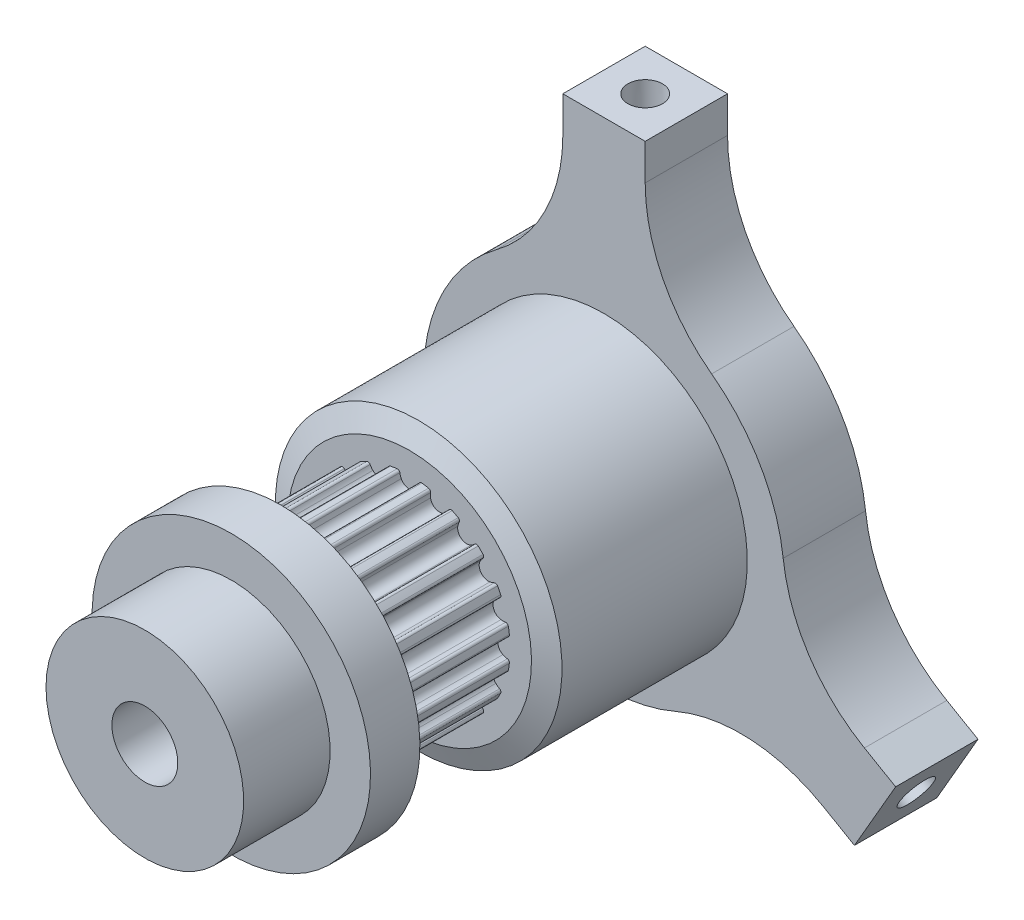
SolidWorks part; units mm, degrees
ref_plane "Front Plane" through (0, 0, 0) normal (0, 0, 1) x (1, 0, 0)
ref_plane "Top Plane" through (0, 0, 0) normal (0, 1, 0) x (1, 0, 0)
ref_plane "Right Plane" through (0, 0, 0) normal (1, 0, 0) x (0, 0, -1)
sketch "Sketch10" plane through (0, 0, 0) normal (0, 0, 1) x (1, 0, 0)
  circle A0 centre (0, 0) radius 2 construction
  dimension "D1" = 4
sketch "Sketch1" plane through (0, 0, 0) normal (0, 0, 1) x (1, 0, 0)
  line L5 (7.9825, -7.4955) -> (15.2045, -11.6651)
  line L6 (10.4825, -3.1653) -> (17.7045, -7.3349)
  line L7 (15.2045, -11.6651) -> (17.7045, -7.3349)
  line L9 (-10.4825, -3.1653) -> (-17.7045, -7.3349)
  line L10 (-7.9825, -7.4955) -> (-15.2045, -11.6651)
  line L11 (-17.7045, -7.3349) -> (-15.2045, -11.6651)
  line L13 (-2.5, 10.6608) -> (-2.5, 19)
  line L14 (2.5, 10.6608) -> (2.5, 19)
  line L15 (-2.5, 19) -> (2.5, 19)
  line L16 (-10.4825, -3.1653) -> (-2.5, 10.6608) construction
  line L17 (2.5, 10.6608) -> (10.4825, -3.1653) construction
  line L18 (-7.9825, -7.4955) -> (7.9825, -7.4955) construction
  line L19 (2.5, 19) -> (17.7045, -7.3349) construction
  line L20 (15.2045, -11.6651) -> (-15.2045, -11.6651) construction
  line L21 (-17.7045, -7.3349) -> (-2.5, 19) construction
  arc A0 (10.4825, -3.1653) -> (2.5, 10.6608) centre (0, 0) ccw
  arc A1 (-2.5, 10.6608) -> (-10.4825, -3.1653) centre (0, 0) ccw
  arc A2 (-7.9825, -7.4955) -> (7.9825, -7.4955) centre (0, 0) ccw
  dimension "D1" = 21.9
  dimension "D2" = 5
  dimension "D3" = 19
extrude "Boss-Extrude1" add sketch "Sketch1" along normal blind 5
sketch "Sketch6" plane through (0, 0, 0) normal (1, 0, 0) x (0, 0, -1)
  line L0 (-5, 0) -> (-5, 8.7)
  line L1 (-5, 8.7) -> (-16.25, 8.7)
  line L2 (-16.25, 8.7) -> (-16.8068, 7.404)
  line L3 (-16.8068, 7.404) -> (-16.8068, 6.1085)
  line L4 (-16.8068, 6.1085) -> (-24.1768, 6.1085)
  line L5 (-24.1768, 6.1085) -> (-24.1768, 7.404)
  line L6 (-24.1768, 7.404) -> (-24.6263, 8.45)
  line L7 (-24.6263, 8.45) -> (-27.6263, 8.45)
  line L8 (-5, 0) -> (-27.6263, 0) construction
  line L9 (-27.6263, 8.45) -> (-27.6263, 0)
  line L10 (-24.1768, 7.404) -> (-24.7337, 8.7) construction
  line L11 (-20.4918, 6.1085) -> (-20.4918, 0) construction
  line L12 (-5, 10.6608) -> (-5, -3.1653) construction
  line L13 (-5, 0) -> (-27.6263, 0)
  line L14 (-24.7337, 8.7) -> (-16.25, 8.7) construction
  line L15 (-20.4918, 8.7) -> (-20.4918, 6.1085) construction
  dimension "D1" = 17.4
  dimension "D2" = 7.37
  dimension "D3" = 8.38
  dimension "D4" = 12.217
  dimension "D5" = 14.808
  dimension "D6" = 11.25
  dimension "D7" = 3
  dimension "D8" = 0.25
revolve "Revolve1" add sketch "Sketch6" angle 360 about L13
sketch "Sketch11" plane through (0, 0, 27.6263) normal (0, 0, 1) x (1, 0, 0)
  circle A2 centre (0, 0) radius 6
  circle A3 centre (0, 0) radius 6
  dimension "D1" = 4
extrude "Boss-Extrude3" add sketch "Sketch11" along normal blind 5.25
sketch "Sketch2" plane through (0, 19, 0) normal (0, 1, 0) x (1, 0, 0)
  line L0 (0, 0) -> (0, -2.5) construction
  line L1 (0, -2.5) -> (2.5, -2.5) construction
  line L2 (2.5, -5) -> (2.5, 0) construction
  circle A0 centre (0, -2.5) radius 1.05
  dimension "D1" = 2.1
extrude "Cut-Extrude1" cut sketch "Sketch2" against normal blind 10
pattern_circular "CirPattern2" count 3 over 360 about axis through (0, 0, 5) along (0, 0, -1) of "Cut-Extrude1"
draft "Draft4" type of draft neutral plane draft angle 1 faces to draft 1 face at (0, 9, 3.55) neutral plane through (-2.5, 19, 5) neutral plane normal (0, 1, 0) parameters "D1"=1
draft "Draft5" type of draft neutral plane draft angle 1 faces to draft 1 face at (-7.7942, -4.5, 3.55) neutral plane through (-17.7045, -7.3349, 5) neutral plane normal (-0.866, -0.5, 0) parameters "D1"=1
draft "Draft6" type of draft neutral plane draft angle 1 faces to draft 1 face at (7.7942, -4.5, 3.55) neutral plane through (15.2045, -11.6651, 5) neutral plane normal (0.866, -0.5, 0) parameters "D1"=1
sketch "Sketch3" plane through (0, 0, 0) normal (0, 0, -1) x (-1, 0, 0)
  circle A0 centre (0, 0) radius 2
  circle A1 centre (0, 0) radius 2 construction
extrude "Cut-Extrude2" cut sketch "Sketch3" against normal through all
sketch "Sketch7" plane through (0, 0, 16.8068) normal (0, 0, 1) x (1, 0, 0)
  point P0 (0, 0)
  line B0 (0, 0) -> (0, 5.3585) construction
  line B1 (-1.8963, 5.8067) -> (-2.841, 8.6995)
  line B2 (-2.841, 8.6995) -> (2.841, 8.6995)
  line B3 (2.841, 8.6995) -> (1.8963, 5.8067)
  arc B4 (-0.4989, 5.6703) -> (0.4989, 5.6703) centre (0, 5.9135) ccw
  arc B5 (-0.4989, 5.6703) -> (-0.5855, 5.9387) centre (0.4, 6.1085) cw
  arc B6 (-1.8963, 5.8067) -> (-0.7518, 6.0621) centre (0, 0) cw
  arc B7 (-0.5855, 5.9387) -> (-0.7518, 6.0621) centre (-0.7333, 5.9132) ccw
  arc B8 (1.8963, 5.8067) -> (0.7518, 6.0621) centre (0, 0) ccw
  arc B9 (0.5855, 5.9387) -> (0.7518, 6.0621) centre (0.7333, 5.9132) cw
  arc B10 (0.4989, 5.6703) -> (0.5855, 5.9387) centre (-0.4, 6.1085) ccw
sketch_block_instance "Block-Gt Timing Belt Pulley Groove-1"
sketch_block "Block-Gt Timing Belt Pulley Groove" parameters "D1"=12.725, "D2"=17.399, "D6"=0.555, "D7"=1, "D9"=0.15, "D3"=9.6972, "D4"=4.8486, "D5"=2, "D8"=0.254, "D10"=0.4, "D11"=0.75
extrude "Cut-Extrude3" cut sketch "Sketch7" along normal up to surface (7.37 mm away) up to face at (0, 7.404, 24.1768)
pattern_circular "CirPattern4" count 20 over 360 about axis through (0, 0, 32.8763) along (0, 0, -1) of "Cut-Extrude3"
fillet "Fillet1" radius 10 6 edges at (2.5, 10.6608, 2.5) (10.4825, -3.1653, 2.5) (7.9825, -7.4955, 2.5) (-7.9825, -7.4955, 2.5) (-10.4825, -3.1653, 2.5) (-2.5, 10.6608, 2.5)
